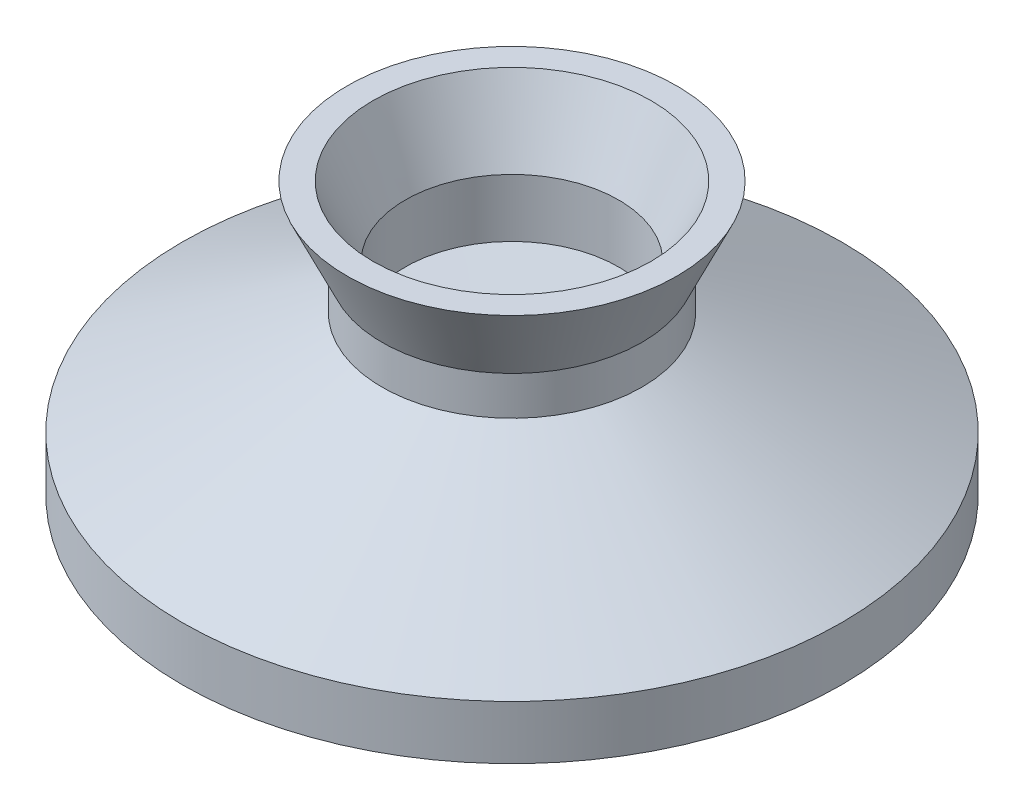
SolidWorks part; units mm, degrees
ref_plane "Front Plane" through (0, 0, 0) normal (0, 0, 1) x (1, 0, 0)
ref_plane "Top Plane" through (0, 0, 0) normal (0, 1, 0) x (1, 0, 0)
ref_plane "Right Plane" through (0, 0, 0) normal (1, 0, 0) x (0, 0, -1)
sketch "Sketch1" plane through (0, 0, 0) normal (0, 0, 1) x (1, 0, 0)
  line L0 (78.4718, -20.4757) -> (4.5, -25)
  line L1 (0, -201655.0005) -> (0, 281095.0265) construction
  line L3 (4.5, -25) -> (4.5, -31)
  line L5 (85, -17.1098) -> (33.5, 9.6994)
  line L6 (33.5, 9.6994) -> (33.5, 19.6994)
  line L8 (78.4718, -20.4757) -> (27.5, 6.0585)
  line L9 (27.5, 6.0585) -> (27.5, 21.0296)
  line L15 (0, -1021.2131) -> (0, 48978.7869) construction
  line L19 (33.5, 19.6994) -> (42.5, 39)
  line L20 (42.5, 39) -> (35.8797, 39)
  line L22 (27.5, 6.0585) -> (27.5, 94) construction
  line L23 (33.5, 9.6994) -> (33.5, 94) construction
  line L24 (35.8797, 39) -> (27.5, 21.0296)
  line L25 (81.2423, -15.1536) -> (33.5, 9.6994) construction
  line L26 (4.5, -31) -> (85, -31)
  line L27 (85, -31) -> (85, -17.1098)
  point P8 (0, 0)
  point P9 (0, 0)
  point P10 (0, 0)
  point P11 (0, 0)
  point P12 (67.5362, -23.4976)
  point P20 (0, 0)
  point P22 (52.0559, -20.6506)
  point P24 (77.3226, -19.3412)
  point P26 (67.7141, -20.1252)
  point P27 (87.2547, -20.4197)
  point P28 (77.2487, -22.4021)
  point P30 (78.6081, -23.3404)
  point P32 (79.4338, -20.1752)
  point P33 (78.2927, -20.5026)
  point P34 (0, 0)
  point P35 (0, 0)
  point P36 (0, 0)
  point P37 (0, 0)
  dimension "D4" = 6
  dimension "D5" = 4.5
  dimension "D7" = 15
  dimension "D9" = 25
  dimension "D12" = 6
  dimension "D14" = 70
  dimension "D13" = 27.5
  dimension "D15" = 10
  dimension "D2" = 85
  dimension "D6" = 27.5
  dimension "D8" = 42.5
  dimension "D10" = 3.5
  dimension "D3" = 6
revolve "Revolve2" add sketch "Sketch1" angle 360 about L15
sketch "Sketch2" plane through (0, 0, 0) normal (0, 0, 1) x (1, 0, 0)
  line L1 (0, -31) -> (81.4732, -22.6761)
  line L2 (81.4732, -22.6761) -> (81.4732, -18.432)
  line L6 (0, -15.0051) -> (72.6459, -15.0051)
  line L8 (72.6459, -15.0051) -> (81.4732, -18.432)
  line L9 (0, -201021.2131) -> (0, 248978.7869) construction
  line L10 (0, -15.0051) -> (0, -31)
  point P2 (0, -25.7782)
  point P4 (0, -28.4966)
  point P6 (59.79, -8.0676)
  point P7 (61.8745, -8.8723)
  point P10 (68.1642, -13.2586)
  point P11 (71.109, -14.6926)
  point P12 (72.6459, -15.458)
  point P13 (0, -29.8143)
  point P14 (0, 0)
  point P15 (0, 0)
  point P16 (0, -32.6386)
  point P17 (0, 0)
revolve "Revolve4" [suppressed] add sketch "Sketch2" angle 360 about L15
other "Intersect1" [suppressed]
equation "\"D4@Sketch1\"=\"D3@Sketch1\""
equation "\"D12@Sketch1\"=\"D3@Sketch1\""
